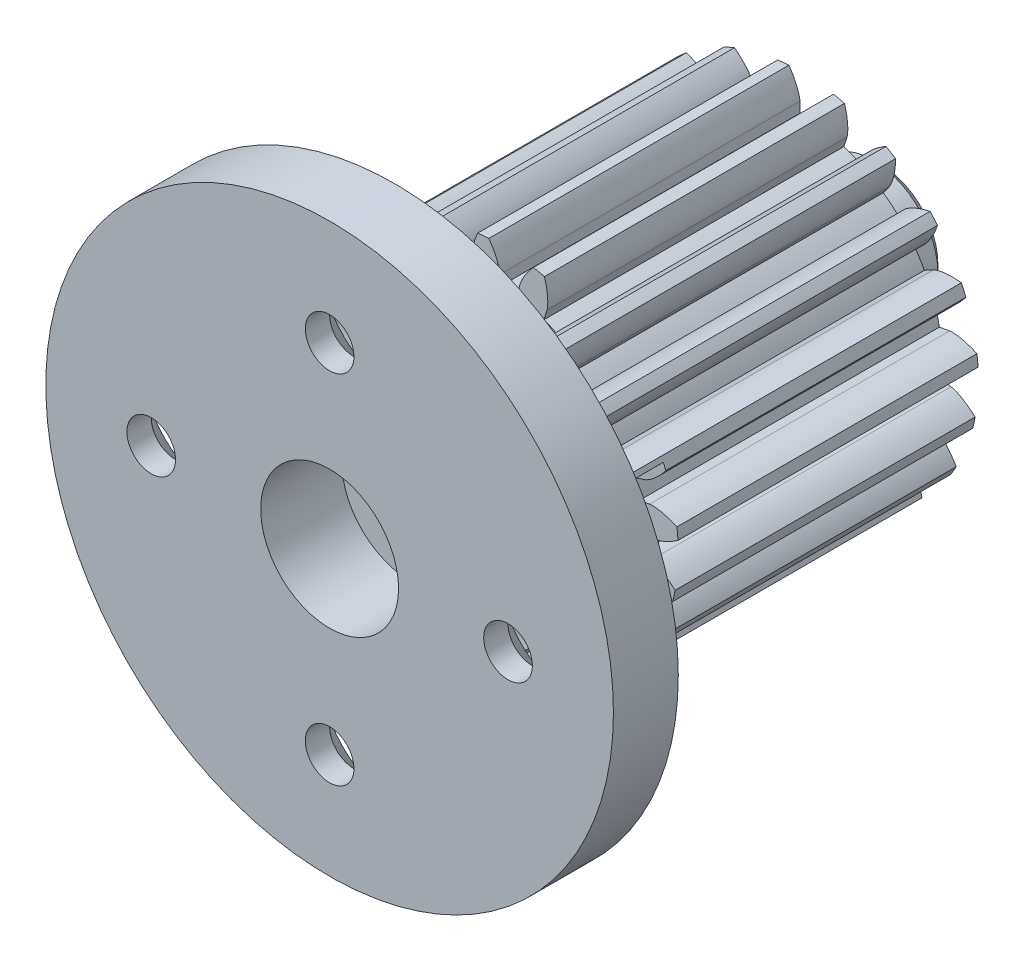
SolidWorks part; units mm, degrees
ref_plane "Front Plane" through (0, 0, 0) normal (0, 0, 1) x (1, 0, 0)
ref_plane "Top Plane" through (0, 0, 0) normal (0, 1, 0) x (1, 0, 0)
ref_plane "Right Plane" through (0, 0, 0) normal (1, 0, 0) x (0, 0, -1)
sketch "Sketch1" plane through (0, 0, 0) normal (0, 0, 1) x (1, 0, 0)
  circle A0 centre (0, 0) radius 11
  dimension "D1" = 22
extrude "Boss-Extrude1" add sketch "Sketch1" along normal mid plane 25
sketch "Sketch2" plane through (0, 0, 0) normal (0, 0, 1) x (1, 0, 0)
  line L0 (0, 0) -> (9.3969, 0) construction
  line L1 (0, 0) -> (9.9798, -0.6359) construction
  line L2 (0, 0) -> (9.3209, -1.1927) construction
  line L3 (9.3969, 0) -> (8.75, 0)
  line L4 (9.3209, -1.1927) -> (8.6792, -1.1106)
  circle A0 centre (0, 0) radius 10 construction
  circle A1 centre (0, 0) radius 9.3969 construction
  circle A2 centre (0, 0) radius 8.75
  circle A3 centre (0, 0) radius 11 construction
  circle A4 centre (0, 0) radius 11
  spline S0 degree 4 poles (9.3969, 0) (9.4001, 0) (9.4091, 0.0003) (9.4262, 0.0014) (9.4539, 0.004) (9.4892, 0.0084) (9.5346, 0.0155) (9.588, 0.0256) (9.6465, 0.0385) (9.7099, 0.0545) (9.7728, 0.0722) (9.8354, 0.0914) (9.8974, 0.112) (9.9723, 0.1386) (10.0615, 0.1728) (10.1651, 0.2163) (10.2816, 0.2695) (10.3992, 0.328) (10.514, 0.389) (10.6287, 0.4546) (10.7389, 0.5208) (10.852, 0.5936) (10.9558, 0.6628) (11.0704, 0.7447) (11.1625, 0.8121) (11.2821, 0.9055) (11.3523, 0.9621) (11.4337, 1.0298) (11.4695, 1.0607) (11.4916, 1.0797) knots 0 0 0 0 0 0.005377 0.015084 0.028532 0.04661 0.064855 0.092111 0.119476 0.146842 0.174209 0.201575 0.228941 0.256307 0.307035 0.361767 0.4165 0.471232 0.525964 0.580697 0.635429 0.690161 0.744894 0.799626 0.854358 0.909091 0.954545 1 1 1 1 1 construction
  spline S1 degree 4 poles (9.3969, 0) (9.4001, 0) (9.4091, 0.0003) (9.4262, 0.0014) (9.4539, 0.004) (9.4892, 0.0084) (9.5346, 0.0155) (9.588, 0.0256) (9.6465, 0.0385) (9.7099, 0.0545) (9.7728, 0.0722) (9.8354, 0.0914) (9.8974, 0.112) (9.9723, 0.1386) (10.0615, 0.1728) (10.1651, 0.2163) (10.2816, 0.2695) (10.3992, 0.328) (10.514, 0.389) (10.6287, 0.4546) (10.7389, 0.5208) (10.852, 0.5936) (10.9558, 0.6628) (11.0704, 0.7447) (11.1625, 0.8121) (11.2562, 0.8853) (11.3016, 0.9214) (11.3247, 0.9401) knots 0 0 0 0 0 0.005377 0.015084 0.028532 0.04661 0.064855 0.092111 0.119476 0.146842 0.174209 0.201575 0.228941 0.256307 0.307035 0.361767 0.4165 0.471232 0.525964 0.580697 0.635429 0.690161 0.744894 0.799626 0.854358 0.909091 0.909091 0.909091 0.909091 0.909091
  spline S2 degree 4 poles (9.3209, -1.1927) (9.3241, -1.1932) (9.333, -1.1946) (9.3497, -1.1978) (9.3769, -1.2039) (9.4113, -1.2128) (9.4555, -1.2256) (9.5072, -1.2424) (9.5636, -1.2626) (9.6244, -1.2865) (9.6846, -1.312) (9.7442, -1.339) (9.8032, -1.3673) (9.874, -1.4032) (9.9582, -1.4485) (10.0554, -1.5047) (10.1642, -1.5723) (10.2734, -1.6453) (10.3795, -1.7204) (10.4851, -1.8) (10.5859, -1.8797) (10.6889, -1.9662) (10.783, -2.0481) (10.8864, -2.1438) (10.9691, -2.2223) (11.076, -2.3302) (11.1384, -2.3952) (11.2105, -2.4727) (11.2421, -2.5079) (11.2616, -2.5296) knots 0 0 0 0 0 0.005377 0.015084 0.028532 0.04661 0.064855 0.092111 0.119476 0.146842 0.174209 0.201575 0.228941 0.256307 0.307035 0.361767 0.4165 0.471232 0.525964 0.580697 0.635429 0.690161 0.744894 0.799626 0.854358 0.909091 0.954545 1 1 1 1 1 construction
  spline S3 degree 4 poles (9.3209, -1.1927) (9.3241, -1.1932) (9.333, -1.1946) (9.3497, -1.1978) (9.3769, -1.2039) (9.4113, -1.2128) (9.4555, -1.2256) (9.5072, -1.2424) (9.5636, -1.2626) (9.6244, -1.2865) (9.6846, -1.312) (9.7442, -1.339) (9.8032, -1.3673) (9.874, -1.4032) (9.9582, -1.4485) (10.0554, -1.5047) (10.1642, -1.5723) (10.2734, -1.6453) (10.3795, -1.7204) (10.4851, -1.8) (10.5859, -1.8797) (10.6889, -1.9662) (10.783, -2.0481) (10.8864, -2.1438) (10.9691, -2.2223) (11.0528, -2.3068) (11.0932, -2.3484) (11.1138, -2.3699) knots 0 0 0 0 0 0.005377 0.015084 0.028532 0.04661 0.064855 0.092111 0.119476 0.146842 0.174209 0.201575 0.228941 0.256307 0.307035 0.361767 0.4165 0.471232 0.525964 0.580697 0.635429 0.690161 0.744894 0.799626 0.854358 0.909091 0.909091 0.909091 0.909091 0.909091
  dimension "D1" = 20
  dimension "D2" = 18.7939
  dimension "D3" = 17.5
  dimension "D4" = 3.646
  dimension "D5" = 3.646
extrude "Cut-Extrude1" cut sketch "Sketch2" against normal through all both and the other way through all contours A2 S3 A4 S1 region at (10.0295, -0.6391, 0)
pattern_circular "CirPattern2" count 20 over 360 about axis through (0, 0, -12.5) along (0, 0, 1) of "Cut-Extrude1"
sketch "Sketch3" plane through (0, 0, 0) normal (0, 1, 0) x (1, 0, 0)
  line L0 (0, 12.5) -> (0, 20.841) construction
  line L1 (0, 20.841) -> (0, -26.4333) construction
  line L2 (0, 17.5) -> (-4, 17.5)
  line L3 (-4, 17.5) -> (-4, 14)
  line L4 (-4, 14) -> (-4.5, 14)
  line L6 (-4.5, 14) -> (-4.5, 12.5)
  line L9 (0, 12.5) -> (-4.5, 12.5)
  line L10 (-0.68, -12.5) -> (0, -12.5) construction
  line L11 (0, -12.5) -> (-17.5, -12.5)
  line L12 (-17.5, -12.5) -> (-17.5, -16.5)
  line L13 (-17.5, -16.5) -> (0, -16.5)
  line L14 (0, 17.5) -> (0, -16.5)
  line L15 (0, 12.5) -> (-0.68, 12.5) construction
  point P7 (0, -12.5)
  point P14 (0, 12.5)
  dimension "D1" = 4
  dimension "D2" = 3.5
  dimension "D3" = 1.5
  dimension "D4" = 0.5
  dimension "D5" = 4
  dimension "D6" = 17.5
revolve "Revolve1" add sketch "Sketch3" angle 360 about L0 region at (-2.0813, 0, -14.9367) region at (-8.75, 0, 14.5)
chamfer "Chamfer1" distance 0.5 angle 45 1 edges at (4.5, 0, -12.5)
chamfer "Chamfer2" distance 0.5 angle 45 1 edges at (4, 0, -17.5)
sketch "Sketch4" plane through (0, 0, 16.5) normal (0, 0, 1) x (1, 0, 0)
  circle A0 centre (0, 0) radius 2.5
  dimension "D1" = 5
extrude "Cut-Extrude2" cut sketch "Sketch4" against normal through all
sketch "Sketch5" plane through (0, 0, 16.5) normal (0, 0, 1) x (1, 0, 0)
  circle A0 centre (0, 0) radius 4.25
  dimension "D1" = 8.5
extrude "Cut-Extrude3" cut sketch "Sketch5" against normal blind 5
sketch "Sketch6" plane through (0, 0, 12.5) normal (0, 0, -1) x (-1, 0, 0)
  circle A0 centre (0, 0) radius 11 construction
  circle A1 centre (0, 11) radius 1.5
  circle A2 centre (11, 0) radius 1.5
  circle A3 centre (0, -11) radius 1.5
  circle A4 centre (-11, 0) radius 1.5
  point P14 (0, 0)
  dimension "D1" = 22
  dimension "D2" = 3
  dimension "D3" = 4
extrude "Cut-Extrude4" cut sketch "Sketch6" against normal through all
sketch "Sketch7" plane through (0, 0, 0) normal (0, 1, 0) x (1, 0, 0)
  line L0 (9.5, -16.5) -> (12.5, -16.5) construction
  line L1 (12.5, -12.5) -> (9.5, -12.5) construction
  line L2 (9.5, -16.5) -> (12.5, -16.5)
  line L4 (11, -12.5) -> (11, -16.5) construction
  line L5 (11, -12.5) -> (15.5, -12.5)
  line L6 (15.5, -12.5) -> (12.5, -15)
  line L7 (12.5, -15) -> (11, -15)
  line L8 (11, -12.5) -> (11, -15)
  dimension "D3" = 1.5
  dimension "D2" = 4.5
  dimension "D1" = 2.5
revolve "Cut-Revolve1" cut sketch "Sketch7" angle 360 about L4 region at (12.625, 0, 13.5417)
pattern_circular "CirPattern3" count 4 over 360 about axis through (0, 0, -17.5) along (0, 0, 1) of "Cut-Revolve1"
sketch "Sketch8" plane through (0, 0, 12.5) normal (0, 0, -1) x (-1, 0, 0)
  line L0 (0, 0) -> (0, 11) construction
  circle A0 centre (0, 11) radius 4.5
  circle A1 centre (11, 0) radius 4.5
  circle A2 centre (0, -11) radius 4.5
  circle A3 centre (-11, 0) radius 4.5
  circle A4 centre (0, 0) radius 11 construction
  point P13 (0, 0)
  dimension "D3" = 4
  dimension "D2" = 9
  dimension "D1" = 11
extrude "Cut-Extrude9" cut sketch "Sketch8" along normal blind 6.5
sketch "Sketch9" plane through (0, 0, 16.5) normal (0, 0, 1) x (1, 0, 0)
  circle A1 centre (0, 0) radius 17.5 construction
  circle A2 centre (0, 0) radius 18.5
  circle A3 centre (0, 0) radius 18.5
  circle A4 centre (0, 0) radius 17.5
  dimension "D1" = 1
extrude "Boss-Extrude2" [suppressed] add sketch "Sketch9" against normal blind 1
equation "\"Ns\"= 20"
equation "\"module\"= 1"
equation "\"pressure angle\"= 20deg"
equation "\"h_a\"= 1 * \"module\"'addendum"
equation "\"h_b\"= 1.25 * \"module\"'dedendum"
equation "\"clr_tip_root\"= \"h_f\" - \"h_a\"'clearance of gear tooth tip and root"
equation "\"dp_s\"= \"module\" * \"Ns\"'PCD"
equation "\"db_s\"= \"dp_s\" * cos ( \"pressure angle\" )'base CD"
equation "\"D1@Sketch1\"=\"dp_s\" + 2*\"h_a\""
equation "\"fw_s_calc\"= 10mm'face width"
equation "\"D1@Boss-Extrude1\"=\"fw_s_used\""
equation "\"D1@Sketch2\"=\"dp_s\""
equation "\"D2@Sketch2\"= \"db_s\""
equation "\"D3@Sketch2\"=\"dp_s\"- 2*\"h_b\""
equation "\"alpha_s\"= sqr ( \"dp_s\" ^ 2 - \"db_s\" ^ 2 ) / \"db_s\" * 180 / pi - \"pressure angle\""
equation "\"D4@Sketch2\"= 360 / ( 4 * \"Ns\" ) - \"alpha_s\""
equation "\"beta_s\"= ( 360 / ( 4 * \"Ns\" ) - \"alpha_s\" ) * 2"
equation "\"D5@Sketch2\"= 360 / ( 4 * \"Ns\" ) - \"alpha_s\""
equation "\"D1@CirPattern2\"=\"Ns\""
equation "\"pressure_angle\"= 20deg"
equation "\"h_f\"= 1.25 * \"module\"'dedendum"
equation "\"bearing_ID\"= \"module\" * ( \"Ns\" + \"Np_b\") + 6"
equation "\"bearing_OD\"= 1.18 * \"bearing_ID\" + 8.57"
equation "\"bearing_height\"= 0.09 * \"bearing_ID\" + 4.62"
equation "\"clearance_planet\"=1.5"
equation "\"case_dist\"= \"sec_carrier_thickness\" + \"clearance_planet\" + \"sun_coupler_hub_thickness\" - \"case_mounting_surface_height\""
equation "\"Motor_case_OD_max\"= \"case_mounting_PCD\" + \"case_mounting_hole_allen_socket_dia\" + \"clearance_case_mount_holes_shell_thickness\" * 2"
equation "\"case_mounting_PCD\"= \"motor_case_OD_base\" + \"case_mounting_hole_shift\" * 2"
equation "\"bearing mount thickness\"= IIF((\"bearing_OD\" + \"output_mounting_hole_dia\" * 4) > (\"Nr_s\" * \"module\" + 2 * \"h_b\"), \"output_mounting_hole_dia\" * 2, ((\"Nr_s\" * \"module\" + 2 * \"h_b\" - (\"bearing_OD\" + \"output_mounting_hole_dia\" * 4)) / 2) + \"output_mounting_hole_dia\" * 2 + \"standard_clearance_1_5mm\")"
equation "\"case_mounting_hole_dia\"=3"
equation "\"output_mounting_PCD\"= \"bearing_OD\" + \"bearing mount thickness\""
equation "\"output_mounting_hole_dia\"= 4"
equation "\"clearance_case_mount_holes_shell_thickness\"= 1"
equation "\"motor_case_OD_base\"= \"motor_OD\" + \"clearance_motor_and_case\" * 2 + \"Motor_case_thickness\" * 2"
equation "\"sec_carrier_thickness\"= 5"
equation "\"sun_coupler_hub_thickness\"= 4"
equation "\"clearance_sun_coupler_sec_carrier\"= 1.5"
equation "\"clearance_motor_and_case\"= IIF( ((\"Ns\" + \"Np_b\" * 2) * \"module\") < \"motor_OD\", 5, (((\"Ns\" + \"Np_b\" * 2) * \"module\" - \"motor_OD\") * 0.5 + 5) )"
equation "\"motor_OD\"= 72"
equation "\"Motor_case_thickness\"= 2.5"
equation "\"Motor_case_ID\"= \"motor_OD\" + \"clearance_motor_and_case\" * 2"
equation "\"case_mounting_hole_shift\"= \"case_mounting_hole_dia\" / 2 - 0.5"
equation "\"output_mounting_nut_wrench_size\"= 7"
equation "\"output_mounting_nut_thickness\"= 3.2"
equation "\"case_mounting_hole_allen_socket_dia\"= 5.5"
equation "\"output_mounting_nut_depth\"= 3"
equation "\"case_mounting_bolt_depth\"= 4.5"
equation "\"ring_radial_thickness\"= 5"
equation "\"ring_to_chamfer_clearance\"= \"clearance_planet\""
equation "\"Motor_case_OD_base_to_chamfer\"=5"
equation "\"pattern_offset_from_motor_case_OD_base\"= 3"
equation "\"pattern_bulge_dia\"= 3"
equation "\"pattern_num_bulge\"= 18"
equation "\"pattern_depth\"= 2"
equation "\"motor_height\"= 27"
equation "\"case_mounting_wrench_size\"= 5.5"
equation "\"case_mounting_nut_clearance\"= 2"
equation "\"base_plate_thickness\"= 4"
equation "\"case_mounting_nut_thickness\"= 2.4"
equation "\"case_mounting_surface_height\"= 4"
equation "\"motor_mount_hole_PCD\"= 32"
equation "\"motor_mount_hole_dia\"= 4"
equation "\"motor_mount_hole_num\"= 4"
equation "\"central_hole_offset_from_motor_mount_PCD\"= 5"
equation "\"wire_slot_dist_from_center\"= 33"
equation "\"wire_slot_length\"= 10"
equation "\"wire_slot_radius\"= 4"
equation "\"driver_upper_holes_dist_from_center\"= 23"
equation "\"driver_lower_holes_dist_from_center\"= 15"
equation "\"driver_side_holes_dist_from_center\"= 20"
equation "\"driver_mount_holes_dia\"= 2.5"
equation "\"driver_mount_inserts_OD\"= 3.5"
equation "\"driver_mount_thickness\"= 1.5"
equation "\"driver_mount_height\"= 4"
equation "\"air_flow_hole_offset\"= 3"
equation "\"num_planet\"= 4"
equation "\"planet_pin_bolt_dia\"= 5"
equation "\"planet_pin_socket_head_dia\"= 8.5"
equation "\"carrier_PCD\"= ( \"Np_b\" + \"Ns\" ) * \"module\""
equation "\"planet_shaft_dia\"= 8"
equation "\"planet_shaft_step_offset\"= 1"
equation "\"carrier_trapezoidal_support_sun_offset\"= 5"
equation "\"carrier_trapezoidal_support_hole_PCD_offset_bearing_ID\"= 4"
equation "\"carrier_trapezoidal_support_hole_dia\"= 3"
equation "\"carrier_trapezoidal_support_hole_socket_head_dia\"= 5.5"
equation "\"carrier_bearing_step_width\"= 1.5"
equation "\"standard_clearance_1_5mm\"=1.5"
equation "\"standard_fillet_1_5mm\"= 1.5"
equation "\"sun_shaft_bearing_OD\"= 12"
equation "\"sun_shaft_bearing_width\"= 3.5"
equation "\"standard_bearing_insertion_chamfer\"= 0.5"
equation "\"carrier_trapezoidal_support_hole_wrench_size\"= 5.5"
equation "\"planet_pin_bolt_wrench_size\"= 8"
equation "\"planet_bearing_OD\"= 12"
equation "\"planet_bearing_width\"= 3.5"
equation "\"planet_bore\"= 10"
equation "\"motor_output_hole_PCD\"= 22"
equation "\"motor_output_hole_dia\"= 3"
equation "\"motor_output_hole_num\"= 4"
equation "\"sun_shaft_bearing_ID\"= 8"
equation "\"D1@Sketch3\"=\"sun_shaft_bearing_ID\"/2"
equation "\"D2@Sketch3\"=\"sun_shaft_bearing_width\" "
equation "\"D3@Sketch3\"=\"standard_clearance_1_5mm\""
equation "\"D4@Sketch3\"=\"standard_clearance_1_5mm\"/3"
equation "\"D5@Sketch3\"=\"sun_coupler_hub_thickness\""
equation "\"sun_hub_dia\"= \"motor_output_hole_PCD\" + \"motor_output_hole_dia\" + \"standard_clearance_1_5mm\" * 2"
equation "\"D1@Chamfer2\"=\"standard_bearing_insertion_chamfer\""
equation "\"D1@Chamfer1\"=\"standard_bearing_insertion_chamfer\""
equation "\"sun_central_bolt_dia\"= 5"
equation "\"sun_central_bolt_socket_head_dia\"= 8.5"
equation "\"D1@Sketch4\"=\"sun_central_bolt_dia\""
equation "\"D1@Cut-Extrude3\"=\"sun_central_bolt_dia\""
equation "\"D1@Sketch5\"=\"sun_central_bolt_socket_head_dia\""
equation "\"fw_s_used\"= \"fw_p_s\" + \"fw_p_b\" + \"clearance_planet\" + \"sec_carrier_thickness\" + \"standard_clearance_1_5mm\" - \"carrier_small_ring_inner_bearing_flap\" +  \"standard_clearance_1_5mm\" "
equation "\"D1@Sketch6\"=\"motor_output_hole_PCD\""
equation "\"D2@Sketch6\"=\"motor_output_hole_dia\""
equation "\"D3@Sketch6\"=\"motor_output_hole_num\""
equation "\"motor_output_hole_CSK_OD\"= 9'8.96 is exact value"
equation "\"motor_output_hole_CSK_head_height\"= 2.5"
equation "\"D2@Sketch7\"=\"motor_output_hole_CSK_OD\"/2"
equation "\"D3@Sketch7\"=\"motor_output_hole_dia\"/2"
equation "\"D1@CirPattern3\"=\"motor_output_hole_num\""
equation "\"Np_b\"= 26"
equation "\"dp_p_b\"= \"module\" * \"Np_b\"'PCD"
equation "\"db_p_b\"= \"dp_p_b\" * cos ( \"pressure angle\" )'base CD"
equation "\"fw_p_s\"= \"fw_r_s\" + \"clearance_planet\""
equation "\"alpha_p_b\"= sqr ( \"dp_p_b\" ^ 2 - \"db_p_b\" ^ 2 ) / \"db_p_b\" * 180 / pi - \"pressure angle\""
equation "\"beta_p_b\"= ( 360 / ( 4 * \"Np_b\" ) - \"alpha_p_b\" ) * 2"
equation "\"bearing_retainer_thickness\"= 2"
equation "\"Np_s\"= 22"
equation "\"fw_p_b\"= 8"
equation "\"dp_p_s\"= \"module\" * \"Np_s\"'PCD"
equation "\"db_p_s\"= \"dp_p_s\" * cos ( \"pressure angle\" )'base CD"
equation "\"alpha_p_s\"= sqr ( \"dp_p_s\" ^ 2 - \"db_p_s\" ^ 2 ) / \"db_p_s\" * 180 / pi - \"pressure angle\""
equation "\"beta_p_s\"= ( 360 / ( 4 * \"Np_s\" ) - \"alpha_p_s\" ) * 2"
equation "\"D1@Sketch8\"=\"motor_output_hole_PCD\"/2"
equation "\"D2@Sketch8\"=\"motor_output_hole_CSK_OD\""
equation "\"D1@Sketch7\"=\"motor_output_hole_CSK_head_height\""
equation "\"D1@Cut-Extrude9\"=\"sec_carrier_thickness\"+\"standard_clearance_1_5mm\""
equation "\"Cut-Extrude9\"= IIF ( ( \"Ns\" * \"module\" + 2 * \"h_a\" ) < ( \"motor_output_hole_PCD\" - \"motor_output_hole_CSK_OD\" ) , \"suppressed\" , \"unsuppressed\" )"
equation "\"D3@Sketch8\"=\"motor_output_hole_num\""
equation "\"Nr_b\"= \"Ns\" + \"Np_b\" * 2"
equation "\"dp_r_b\"= \"module\" * \"Nr_b\"'PCD"
equation "\"db_r_b\"= \"dp_r_b\" * cos ( \"pressure_angle\" )'base CD"
equation "\"fw_r_b\"= \"fw_p_b\"'face width"
equation "\"alpha_r_b\"= sqr ( \"dp_r_b\" ^ 2 - \"db_r_b\" ^ 2 ) / \"db_r_b\" * 180 / pi - \"pressure_angle\""
equation "\"beta_r_b\"= ( 360 / ( 4 * \"Nr_b\" ) + \"alpha_r_b\" ) * 2"
equation "\"ring_OD_b\"= \"Nr_b\" * \"module\" + \"ring_radial_thickness\" * 2"
equation "\"Fillet10\"= IIF ( \"ring_OD_b\" > ( \"bearing_OD\" + 2 * \"bearing mount thickness\" ) , \"suppressed\" , \"unsuppressed\" )"
equation "\"Fillet11\"= IIF ( \"ring_OD_b\" < ( \"bearing_OD\" + 2 * \"bearing mount thickness\" ) , \"suppressed\" , \"unsuppressed\" )"
equation "\"Nr_s\"= \"Ns\" + \"Np_b\" + \"Np_s\"'num teeth"
equation "\"clr_tip_root_s\"= \"h_f\" - \"h_a\"'clearance of gear tooth tip and root"
equation "\"dp_r_s\"= \"module\" * \"Nr_s\"'PCD"
equation "\"db_r_s\"= \"dp_r_s\" * cos ( \"pressure_angle\" )'base CD"
equation "\"fw_r_s\"= 8mm'face width"
equation "\"alpha_r_s\"= sqr ( \"dp_r_s\" ^ 2 - \"db_r_s\" ^ 2 ) / \"db_r_s\" * 180 / pi - \"pressure_angle\""
equation "\"beta_r_s\"= ( 360 / ( 4 * \"Nr_s\" ) + \"alpha_r_s\" ) * 2"
equation "\"small_ring_case_thickness\"= 4mm"
equation "\"carrier_thickness\"= 4mm"
equation "\"small_ring_output_wall_thickness\"= 5mm"
equation "\"small_ring_output_wall_to_bearing_shaft_attachement_hole_dia\"= 4mm"
equation "\"small_ring_output_wall_to_bearing_shaft_attachement_hole_depth\"= 6.5mm"
equation "\"small_ring_output_wall_to_bearing_shaft_attachement_nut_wrench\"= 7mm"
equation "\"small_ring_output_wall_to_bearing_shaft_attachement_nut_thickness\"= 3.2mm"
equation "\"small_ring_output_wall_to_bearing_shaft_attachement_hole_pcd\"= 12mm"
equation "\"small_ring_output_wall_to_bearing_shaft_attachement_hole_num\"= 3"
equation "\"small_ring_output_wall_to_bearing_shaft_attachement_hole_CSK_OD\"= 9mm"
equation "\"small_ring_output_wall_to_bearing_shaft_attachement_hole_CSK_head_height\"= 2.5mm"
equation "\"carrier_small_ring_inner_bearing_ID\"= 20mm"
equation "\"carrier_small_ring_inner_bearing_OD\"= 32mm"
equation "\"carrier_small_ring_inner_bearing_height\"= 7mm"
equation "\"carrier_small_ring_inner_bearing_flap\"= 2mm"
equation "\"gear_casing_big_ring_to_bearing_dist\"=\"fw_p_s\" + \"clearance_planet\" + \"carrier_thickness\" + \"standard_clearance_1_5mm\"*2/3 + \"small_ring_case_thickness\" "
equation "\"gear_casing_thickness\"= 4"
